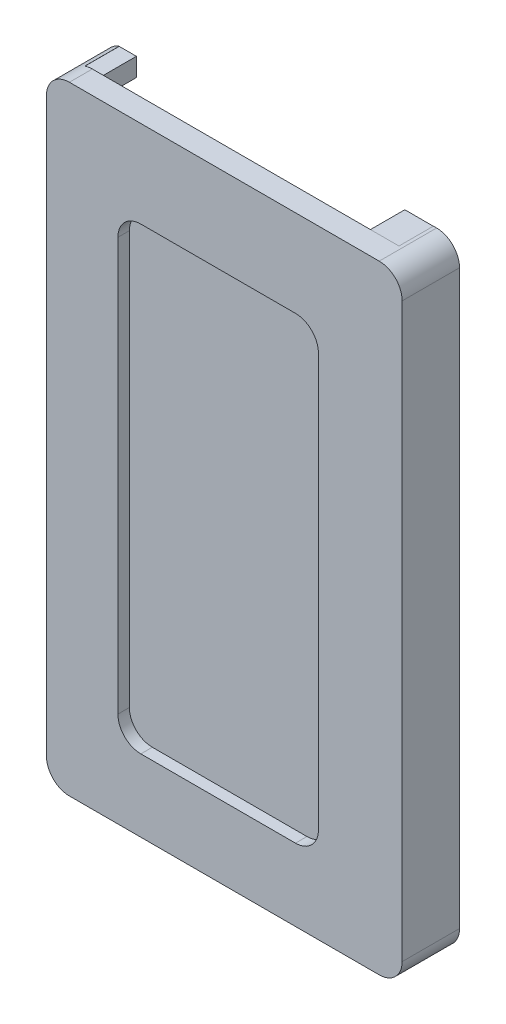
SolidWorks part; units mm, degrees
ref_plane "Front Plane" through (0, 0, 0) normal (0, 0, 1) x (1, 0, 0)
ref_plane "Top Plane" through (0, 0, 0) normal (0, 1, 0) x (1, 0, 0)
ref_plane "Right Plane" through (0, 0, 0) normal (1, 0, 0) x (0, 0, -1)
sketch "草图5" plane through (0, 0, 15) normal (0, 0, 1) x (1, 0, 0)
  line L0 (68.0762, -26.8877) -> (68.0762, -76.7564) construction
  line L1 (37.0762, -24.8877) -> (68.0762, -24.8877)
  line L2 (37.0762, -24.8877) -> (37.0762, -78.7564)
  line L3 (37.0762, -78.7564) -> (68.0762, -78.7564)
  line L4 (68.0762, -24.8877) -> (68.0762, -78.7564)
  line L5 (38.4139, -24.8877) -> (38.4139, -28.6161) construction
  line L6 (38.4139, -26.7519) -> (65.7955, -26.7519)
  line L7 (38.4139, -26.7519) -> (38.4139, -77.1753)
  line L8 (38.4139, -77.1753) -> (65.7955, -77.1753)
  line L9 (65.7955, -26.7519) -> (65.7955, -77.1753)
extrude "凸台-拉伸3" add sketch "草图5" along normal blind 3 contours L2 L1 L4 L3 | L7 L6 L9 L8
sketch "草图8" plane through (0, 0, 15) normal (0, 0, -1) x (-1, 0, 0)
  line L0 (-38.4139, -77.1753) -> (-65.7955, -77.1753) construction
  line L1 (-55.1901, -77.1753) -> (-40.1901, -77.1753)
  line L2 (-55.1901, -77.1753) -> (-55.1901, -78.7564)
  line L3 (-55.1901, -78.7564) -> (-40.1901, -78.7564)
  line L4 (-40.1901, -77.1753) -> (-40.1901, -78.7564)
  line L5 (-37.0762, -78.7564) -> (-68.0762, -78.7564) construction
extrude "切除-拉伸6" cut sketch "草图8" against normal blind 1 contours L2 L1 L4 L3
sketch "草图9" plane through (0, 0, 18) normal (0, 0, 1) x (1, 0, 0)
  line L1 (37.0762, -24.8877) -> (68.0762, -24.8877)
  line L2 (37.0762, -24.8877) -> (37.0762, -78.7564)
  line L3 (37.0762, -78.7564) -> (68.0762, -78.7564)
  line L4 (68.0762, -24.8877) -> (68.0762, -78.7564)
extrude "凸台-拉伸5" add sketch "草图9" along normal blind 2
sketch "草图10" plane through (0, 0, 20) normal (0, 0, 1) x (1, 0, 0)
  line L1 (43.3021, -32.4774) -> (60.7771, -32.4774)
  line L2 (43.3021, -32.4774) -> (43.3021, -72.4639)
  line L3 (43.3021, -72.4639) -> (60.7771, -72.4639)
  line L4 (60.7771, -32.4774) -> (60.7771, -72.4639)
extrude "切除-拉伸7" cut sketch "草图10" against normal blind 1
fillet "圆角1" radius 2 4 edges at (68.0762, -78.7564, 17.5) (37.0762, -78.7564, 17.5) (37.0762, -24.8877, 17.5) (68.0762, -24.8877, 17.5)
fillet "圆角2" radius 2 4 edges at (43.3021, -72.4639, 19.5) (60.7771, -72.4639, 19.5) (60.7771, -32.4774, 19.5) (43.3021, -32.4774, 19.5)
sketch "草图11" plane through (0, -26.7519, 0) normal (0, -1, 0) x (-1, 0, 0)
  line L0 (-65.7955, -18) -> (-65.7955, -15) construction
  line L1 (-38.4139, -15) -> (-65.7955, -15) construction
  line L2 (-38.4139, -18) -> (-65.7955, -18) construction
  line L3 (-38.4139, -18) -> (-38.4139, -15) construction
  line L4 (-65.7955, -18) -> (-65.7955, -15)
  line L5 (-38.4139, -15) -> (-65.7955, -15)
  line L6 (-38.4139, -18) -> (-65.7955, -18)
  line L7 (-38.4139, -18) -> (-38.4139, -15)
extrude "切除-拉伸8" cut sketch "草图11" against normal blind 2
sketch "草图14" plane through (0, 0, 18) normal (0, 0, -1) x (-1, 0, 0)
  line L0 (-65.8048, -24.8943) -> (-63.3048, -24.8943) construction
  line L1 (-65.8048, -24.8943) -> (-63.3048, -24.8943)
  line L2 (-65.8048, -24.8943) -> (-63.3048, -24.8943)
  line L3 (-65.8048, -24.8943) -> (-63.3048, -24.8943)
  line L4 (-65.7955, -77.1753) -> (-38.4139, -77.1753)
  line L5 (-38.4139, -77.1753) -> (-38.4139, -25.0005)
  line L6 (-39.0762, -24.8877) -> (-65.7955, -24.8877)
  line L7 (-65.7955, -24.8877) -> (-65.7955, -77.1753)
  line L9 (-38.4139, -26.6161) -> (-38.4139, -25.0005)
  line L11 (-65.7955, -24.8877) -> (-65.7955, -26.6161)
  line L12 (-38.4139, -25.0096) -> (-39.9139, -25.0096) construction
  line L13 (-39.9139, -25.0096) -> (-39.9139, -26.6161) construction
  line L14 (-38.4139, -26.6161) -> (-39.9139, -26.6161) construction
  line L15 (-65.7955, -26.6161) -> (-63.3048, -26.6161) construction
  line L16 (-63.3048, -24.8943) -> (-63.3048, -26.6161) construction
  line L17 (-38.4139, -25.0096) -> (-39.9139, -25.0096)
  line L18 (-39.9139, -25.0096) -> (-39.9139, -26.6161)
  line L19 (-38.4139, -26.6161) -> (-39.9139, -26.6161)
  line L20 (-65.7955, -26.6161) -> (-63.3048, -26.6161)
  line L21 (-65.8048, -24.8943) -> (-63.3048, -24.8943)
  line L22 (-63.3048, -24.8943) -> (-63.3048, -26.6161)
  arc A1 (-38.4139, -25.0005) -> (-39.0762, -24.8877) centre (-39.0762, -26.8877) ccw
  line M7 (-38.4139, -77.1753) -> (-38.4139, -25.0005)
  line M10 (-65.7955, -24.8877) -> (-65.7955, -77.1753)
  dimension "D1" = 0
extrude "凸台-拉伸6" add sketch "草图14" along normal blind 3 contours L22 L1 L20 M10 | L19 L17 L18 M7 region at (64.5502, -25.7552, 18) region at (39.1639, -25.8129, 18)
